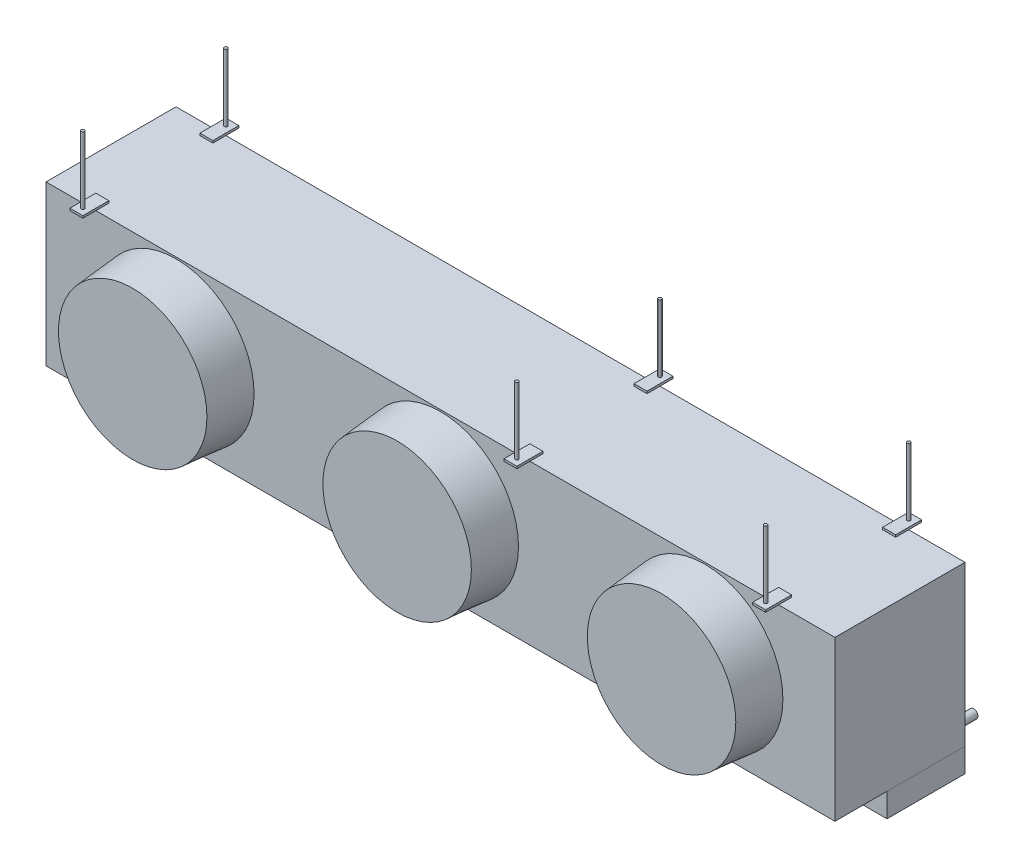
SolidWorks part; units mm, degrees
ref_plane "Front" through (0, 0, 0) normal (0, 0, 1) x (1, 0, 0)
ref_plane "Top" through (0, 0, 0) normal (0, 1, 0) x (1, 0, 0)
ref_plane "Right" through (0, 0, 0) normal (1, 0, 0) x (0, 0, -1)
sketch "Sketch1" plane through (0, 0, 0) normal (0, 1, 0) x (1, 0, 0)
  line L1 (-1155.7, 190.5) -> (1155.7, 190.5)
  line L2 (-1155.7, 190.5) -> (-1155.7, -190.5)
  line L3 (-1155.7, -190.5) -> (1155.7, -190.5)
  line L4 (1155.7, 190.5) -> (1155.7, -190.5)
  line L5 (-1155.7, 190.5) -> (1155.7, -190.5) construction
  line L6 (-1155.7, -190.5) -> (1155.7, 190.5) construction
  point P0 (0, 0)
  dimension "D1" = 2311.4
  dimension "D2" = 381
extrude "Boss-Extrude1" add sketch "Sketch1" along normal blind 466.725
sketch "Sketch2" plane through (0, 0, 190.5) normal (0, 0, 1) x (1, 0, 0)
  line L0 (0, 0) -> (0, 466.725) construction
  line L1 (-1155.7, 466.725) -> (1155.7, 466.725) construction
  line L2 (0, 233.3625) -> (-1155.7, 233.3625) construction
  line L3 (-1155.7, 466.725) -> (-1155.7, 0) construction
  line L4 (0, 233.3625) -> (1155.7, 233.3625) construction
  line L5 (1155.7, 466.725) -> (1155.7, 0) construction
  circle A0 centre (0, 233.3625) radius 228.6
  circle A1 centre (774.7, 233.3625) radius 228.6
  circle A2 centre (-774.7, 233.3625) radius 228.6
  dimension "D1" = 457.2
  dimension "D3" = 381
  dimension "D2" = 381
extrude "Boss-Extrude2" add sketch "Sketch2" along normal blind 127 draft 5
sketch "Sketch3" plane through (0, 466.725, 0) normal (0, 1, 0) x (1, 0, 0)
  line L0 (1155.7, 190.5) -> (-1155.7, 190.5) construction
  line L1 (223.9137, 228.6) -> (262.0137, 228.6)
  line L2 (223.9137, 228.6) -> (223.9137, 152.4)
  line L3 (223.9137, 152.4) -> (262.0137, 152.4)
  line L4 (262.0137, 228.6) -> (262.0137, 152.4)
  line L5 (223.9137, 228.6) -> (262.0137, 152.4) construction
  line L6 (223.9137, 152.4) -> (262.0137, 228.6) construction
  line L8 (223.9137, -152.4) -> (262.0137, -152.4)
  line L9 (223.9137, -152.4) -> (223.9137, -228.6)
  line L10 (223.9137, -228.6) -> (262.0137, -228.6)
  line L11 (262.0137, -152.4) -> (262.0137, -228.6)
  line L12 (223.9137, -152.4) -> (262.0137, -228.6) construction
  line L13 (223.9137, -228.6) -> (262.0137, -152.4) construction
  line L14 (546.1, -190.5) -> (1003.3, -190.5) construction
  line L15 (952.5, 228.6) -> (990.6, 228.6)
  line L16 (952.5, 228.6) -> (952.5, 152.4)
  line L17 (952.5, 152.4) -> (990.6, 152.4)
  line L18 (990.6, 228.6) -> (990.6, 152.4)
  line L19 (952.5, 228.6) -> (990.6, 152.4) construction
  line L20 (952.5, 152.4) -> (990.6, 228.6) construction
  line L21 (952.5, -152.4) -> (990.6, -152.4)
  line L22 (952.5, -152.4) -> (952.5, -228.6)
  line L23 (952.5, -228.6) -> (990.6, -228.6)
  line L24 (990.6, -152.4) -> (990.6, -228.6)
  line L25 (952.5, -152.4) -> (990.6, -228.6) construction
  line L26 (952.5, -228.6) -> (990.6, -152.4) construction
  line L27 (-1003.3, -190.5) -> (-546.1, -190.5) construction
  line L28 (-1047.75, 228.6) -> (-1009.65, 228.6)
  line L29 (-1047.75, 228.6) -> (-1047.75, 152.4)
  line L30 (-1047.75, 152.4) -> (-1009.65, 152.4)
  line L31 (-1009.65, 228.6) -> (-1009.65, 152.4)
  line L32 (-1047.75, 228.6) -> (-1009.65, 152.4) construction
  line L33 (-1047.75, 152.4) -> (-1009.65, 228.6) construction
  line L34 (-1047.75, -152.4) -> (-1009.65, -152.4)
  line L35 (-1047.75, -152.4) -> (-1047.75, -228.6)
  line L36 (-1047.75, -228.6) -> (-1009.65, -228.6)
  line L37 (-1009.65, -152.4) -> (-1009.65, -228.6)
  line L38 (-1047.75, -152.4) -> (-1009.65, -228.6) construction
  line L39 (-1047.75, -228.6) -> (-1009.65, -152.4) construction
  line L40 (-1028.7, -190.5) -> (-1028.7, 190.5) construction
  line L41 (971.55, 190.5) -> (971.55, -190.5) construction
  line L42 (-1028.7, 190.5) -> (0, 190.5) construction
  line L43 (0, 190.5) -> (971.55, 190.5) construction
  line L44 (0, 190.5) -> (971.55, 190.5) construction
  line L45 (-1028.7, 228.6) -> (-1028.7, 209.55) construction
  line L46 (-1028.7, -228.6) -> (-1028.7, -209.55) construction
  line L47 (242.9637, 209.55) -> (242.9637, 190.5) construction
  line L48 (242.9637, -209.55) -> (242.9637, -228.6) construction
  line L49 (971.55, 190.5) -> (971.55, 209.55) construction
  line L50 (971.55, -190.5) -> (971.55, -209.55) construction
  line L51 (-1155.7, 0) -> (-1028.7, 0) construction
  line L53 (-1155.7, 190.5) -> (-1155.7, -190.5) construction
  line L54 (-1155.7, -190.5) -> (1155.7, -190.5) construction
  circle A0 centre (-1028.7, 209.55) radius 4.7625
  circle A1 centre (-1028.7, -209.55) radius 4.7625
  circle A2 centre (971.55, 209.55) radius 4.7625
  circle A3 centre (971.55, -209.55) radius 4.7625
  circle A4 centre (242.9637, -209.55) radius 4.7625
  circle A5 centre (242.9637, 209.55) radius 4.7625
  point P0 (242.9637, 190.5)
  point P7 (242.9637, -190.5)
  point P14 (971.55, 190.5)
  point P19 (971.55, -190.5)
  point P26 (-1028.7, 190.5)
  point P31 (-1028.7, -190.5)
  dimension "D2" = 9.525
  dimension "D5" = 419.1
  dimension "D1" = 127
  dimension "D3" = 19.05
  dimension "D4" = 38.1
  dimension "D6" = 2000.25
  dimension "D7" = 728.5863
extrude "Boss-Extrude3" add sketch "Sketch3" along normal blind 6.35
sketch "Sketch4" plane through (0, 466.725, 0) normal (0, 1, 0) x (1, 0, 0)
  circle A0 centre (-1028.7, 209.55) radius 4.7625 construction
  circle A1 centre (-1028.7, 209.55) radius 4.7625
  circle A2 centre (-1028.7, -209.55) radius 4.7625 construction
  circle A3 centre (-1028.7, -209.55) radius 4.7625
  circle A4 centre (242.9637, -209.55) radius 4.7625 construction
  circle A5 centre (242.9637, -209.55) radius 4.7625
  circle A6 centre (242.9637, 209.55) radius 4.7625 construction
  circle A7 centre (242.9637, 209.55) radius 4.7625
  circle A8 centre (971.55, 209.55) radius 4.7625 construction
  circle A9 centre (971.55, 209.55) radius 4.7625
  circle A10 centre (971.55, -209.55) radius 4.7625 construction
  circle A11 centre (971.55, -209.55) radius 4.7625
extrude "Boss-Extrude4" add sketch "Sketch4" along normal blind 203.2 separate body
sketch "Sketch5" plane through (0, 0, 0) normal (0, -1, 0) x (1, 0, 0)
  line L0 (0, 0) -> (0, -76.2) construction
  line L2 (-1155.7, 38.1) -> (1155.7, 38.1)
  line L3 (-1155.7, 38.1) -> (-1155.7, -190.5)
  line L4 (-1155.7, -190.5) -> (1155.7, -190.5)
  line L5 (1155.7, 38.1) -> (1155.7, -190.5)
  line L6 (-1155.7, 38.1) -> (1155.7, -190.5) construction
  line L7 (-1155.7, -190.5) -> (1155.7, 38.1) construction
  dimension "D1" = 228.6
extrude "Boss-Extrude5" add sketch "Sketch5" along normal blind 69.85 separate body
sketch "Sketch6" plane through (0, -69.85, 0) normal (0, -1, 0) x (1, 0, 0)
  line L0 (0, 38.1) -> (0, -190.5) construction
  line L1 (1155.7, 38.1) -> (-1155.7, 38.1) construction
  line L2 (-1155.7, -190.5) -> (1155.7, -190.5) construction
  circle A0 centre (0, -76.2) radius 12.7
  circle A1 centre (0, -76.2) radius 11.1125
  dimension "D1" = 25.4
  dimension "D2" = 22.225
extrude "Boss-Extrude6" add sketch "Sketch6" along normal blind 44.45
sketch "Sketch7" plane through (0, 0, -190.5) normal (0, 0, -1) x (-1, 0, 0)
  line L0 (0, 0) -> (0, 19.05) construction
  line L1 (0, 19.05) -> (-1104.9, 19.05) construction
  line L2 (0, 19.05) -> (1104.9, 19.05) construction
  line L3 (-1155.7, 466.725) -> (-1155.7, 0) construction
  line L4 (-1155.7, 0) -> (1155.7, 0) construction
  circle A0 centre (-1104.9, 19.05) radius 12.7
  circle A1 centre (1104.9, 19.05) radius 12.7
  dimension "D1" = 25.4
  dimension "D2" = 50.8
  dimension "D3" = 19.05
extrude "Boss-Extrude7" add sketch "Sketch7" along normal blind 76.2
